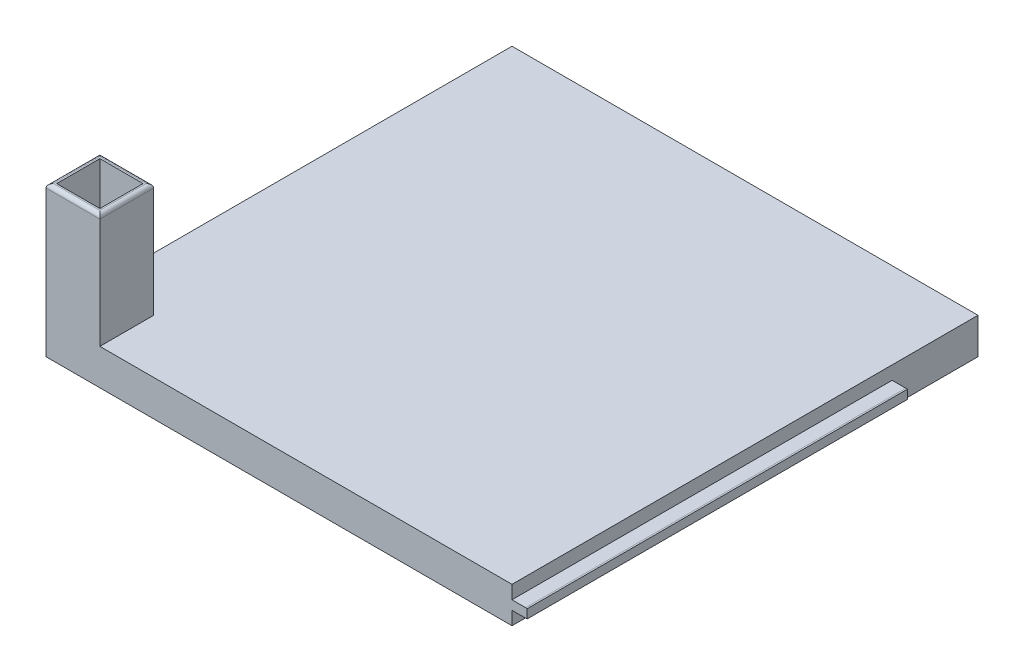
SolidWorks part; units mm, degrees
ref_plane "Front Plane" through (0, 0, 0) normal (0, 0, 1) x (1, 0, 0)
ref_plane "Top Plane" through (0, 0, 0) normal (0, 1, 0) x (1, 0, 0)
ref_plane "Right Plane" through (0, 0, 0) normal (1, 0, 0) x (0, 0, -1)
sketch "Sketch1" plane through (0, 0, 0) normal (0, 1, 0) x (1, 0, 0)
  line L1 (-22.3212, 15.875) -> (133.3788, 15.875)
  line L2 (-22.3212, 15.875) -> (-22.3212, -139.825)
  line L3 (-22.3212, -139.825) -> (133.3788, -139.825)
  line L4 (133.3788, 15.875) -> (133.3788, -139.825)
  line L5 (55.5288, -139.825) -> (55.5288, 15.875) construction
  line L6 (-22.3212, -61.975) -> (133.3788, -61.975) construction
  point P325 (-5.0492, -43.053)
  point P443 (-5.0492, -43.053)
  point P524 (55.5288, -61.975)
  dimension "D1" = 155.7
  dimension "D2" = 155.7
extrude "Boss-Extrude2" add sketch "Sketch1" along normal blind 12
sketch "Sketch2" plane through (0, 12, 0) normal (0, 1, 0) x (1, 0, 0)
  line L1 (-22.3212, -139.825) -> (-4.3212, -139.825)
  line L2 (-22.3212, -139.825) -> (-22.3212, -121.825)
  line L3 (-22.3212, -121.825) -> (-4.3212, -121.825)
  line L4 (-4.3212, -139.825) -> (-4.3212, -121.825)
  line L5 (-13.3212, -121.825) -> (-13.3212, -139.825) construction
  line L6 (-22.3212, -130.825) -> (-12.1612, -130.825) construction
  point P204 (-13.3212, -130.825)
  dimension "D1" = 18
  dimension "D2" = 18
extrude "Boss-Extrude3" add sketch "Sketch2" along normal blind 38.1
sketch "Sketch3" plane through (0, 0, 139.825) normal (0, 0, 1) x (1, 0, 0)
  line L0 (133.3788, 12) -> (133.3788, 0) construction
  line L1 (133.3788, 7.524) -> (138.4588, 7.524)
  line L2 (133.3788, 7.524) -> (133.3788, 4.476)
  line L3 (133.3788, 4.476) -> (138.4588, 4.476)
  line L4 (138.4588, 7.524) -> (138.4588, 4.476)
  line L5 (135.9188, 4.476) -> (135.9188, 7.524) construction
  line L6 (133.3788, 6) -> (138.4588, 6) construction
  line L7 (133.3788, 7.524) -> (133.3788, 12) construction
  line L8 (133.3788, 0) -> (135.9188, 4.476) construction
  line L9 (133.3788, 12) -> (135.9188, 7.524) construction
  point P1032 (135.9188, 6)
  dimension "D1" = 5.08
  dimension "D2" = 3.048
extrude "Boss-Extrude4" add sketch "Sketch3" against normal blind 127
chamfer "Chamfer1" distance 0.508 angle 4 1 edges at (138.4588, 7.524, 76.325) first distance on face at (135.9188, 7.524, 76.325)
chamfer "Chamfer2" distance 0.508 angle 4 1 edges at (138.4588, 4.476, 76.325) first distance on face at (135.9188, 4.476, 76.325)
sketch "Sketch4" plane through (-22.3212, 0, 0) normal (-1, 0, 0) x (0, 0, 1)
  line L0 (-15.875, 12) -> (-15.875, 0) construction
  line L1 (-15.875, 7.5875) -> (-10.541, 7.5875)
  line L2 (-15.875, 7.5875) -> (-15.875, 4.4125)
  line L3 (-15.875, 4.4125) -> (-10.541, 4.4125)
  line L4 (-10.541, 7.5875) -> (-10.541, 4.4125)
  line L5 (-13.208, 4.4125) -> (-13.208, 7.5875) construction
  line L6 (-15.875, 6) -> (-10.541, 6) construction
  line L7 (-15.875, 12) -> (-13.208, 7.5875) construction
  line L8 (-15.875, 0) -> (-13.208, 4.4125) construction
  point P456 (-13.208, 6)
  dimension "D1" = 5.334
  dimension "D2" = 3.175
  dimension "D3" = 5.1559
extrude "Cut-Extrude3" cut sketch "Sketch4" against normal blind 149.86 contours L2 L1 L4 L3
shell "Shell1" thickness 1.778 removed face at (-13.3212, 50.1, 130.825)
fillet "Fillet1" radius 1.27 4 edges at (-22.3212, 50.1, 130.825) (-13.3212, 50.1, 139.825) (-4.3212, 50.1, 130.825) (-13.3212, 50.1, 121.825) type face fillet first side face at (-13.3212, 50.1, 130.825) second side face at (-4.3212, 31.05, 130.825) second side face at (86.0875, 13.35, 139.825) second side face at (-22.3212, 14.82, 43.8718) second side face at (-13.3212, 31.05, 121.825)
